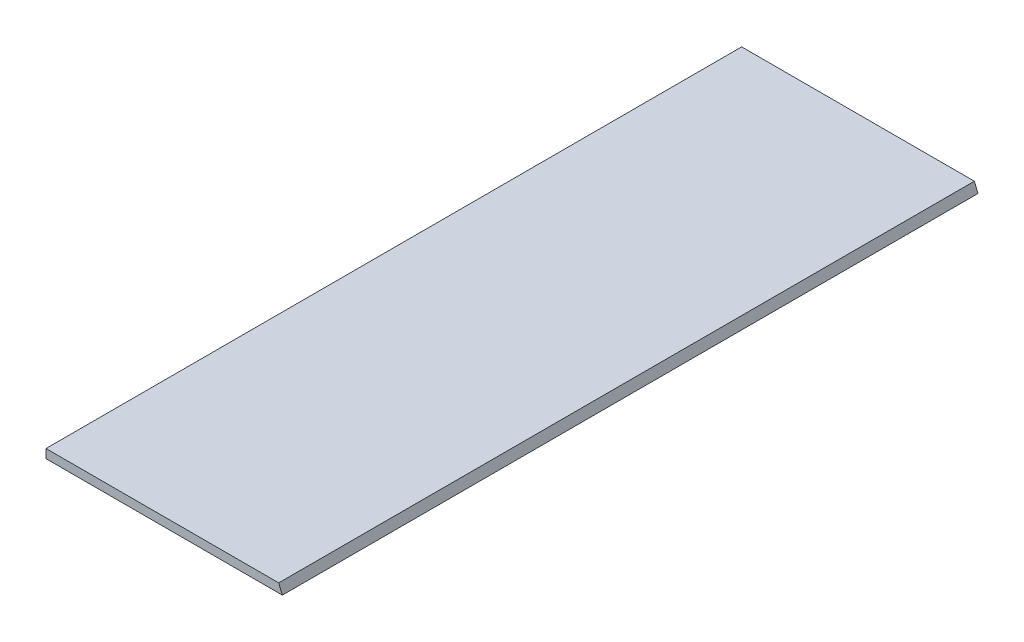
SolidWorks part; units mm, degrees
ref_plane "Front Plane" through (0, 0, 0) normal (0, 0, 1) x (1, 0, 0)
ref_plane "Top Plane" through (0, 0, 0) normal (0, 1, 0) x (1, 0, 0)
ref_plane "Right Plane" through (0, 0, 0) normal (1, 0, 0) x (0, 0, -1)
sketch "Sketch1" plane through (0, 0, 0) normal (0, 0, 1) x (1, 0, 0)
  line L0 (0, 0) -> (0, 6.35)
  line L1 (0, 6.35) -> (167.8037, 6.35)
  line L2 (167.8037, 6.35) -> (170.434, 0)
  line L3 (170.434, 0) -> (0, 0)
  dimension "D1" = 6.35
  dimension "D2" = 170.434
  dimension "D3" = 67.5
extrude "Boss-Extrude1" add sketch "Sketch1" along normal blind 501.65
